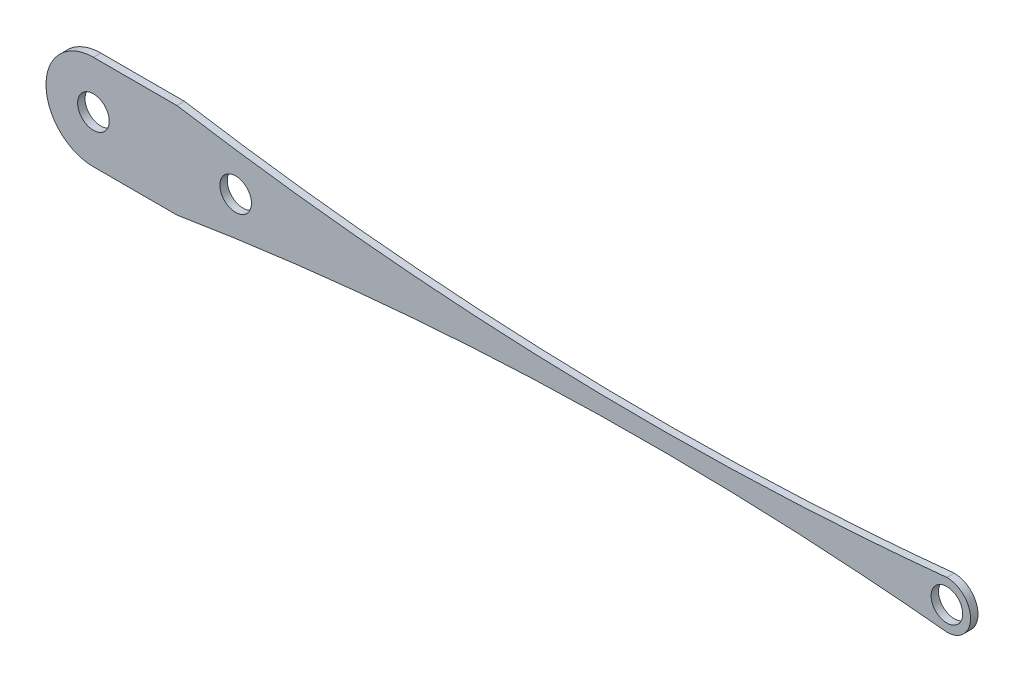
SolidWorks part; units mm, degrees
ref_plane "Front Plane" through (0, 0, 0) normal (0, 0, 1) x (1, 0, 0)
ref_plane "Top Plane" through (0, 0, 0) normal (0, 1, 0) x (1, 0, 0)
ref_plane "Right Plane" through (0, 0, 0) normal (1, 0, 0) x (0, 0, -1)
sketch "Sketch4" plane through (0, 0, 0) normal (0, 0, 1) x (1, 0, 0)
  line L0 (0, 0) -> (457.2, 0) construction
  line L1 (0, 25.4) -> (44.7423, 25.4)
  line L2 (0, -25.4) -> (44.7423, -25.4)
  arc A0 (0, 25.4) -> (0, -25.4) centre (0, 0) ccw
  circle A2 centre (0, 0) radius 8.4667
  circle A3 centre (76.2, 0) radius 8.4667
  circle A4 centre (457.2, 0) radius 8.4667
  arc A5 (457.2, -12.7) -> (457.2, 12.7) centre (457.2, 0) ccw
  arc A6 (44.7423, 25.4) -> (52.6769, 24.1289) centre (44.7423, 0) cw
  arc A7 (52.6769, -24.1289) -> (44.7423, -25.4) centre (44.7423, 0) cw
  spline S0 degree 2 poles (44.7423, 25.4) (249.9499, -8.0007) (457.2, 12.7) knots 0 0 0 1 1 1
  spline S1 degree 2 poles (44.7423, -25.4) (249.9499, 8.0007) (457.2, -12.7) knots 0 0 0 1 1 1
  point P3 (228.6, 0)
  dimension "D3" = 16.9333
  dimension "D5" = 25.4
  dimension "D1" = 50.8
  dimension "D2" = 457.2
  dimension "D6" = 19.05
  dimension "D7" = 19.05
  dimension "D8" = 76.2
extrude "Boss-Extrude2" add sketch "Sketch4" along normal blind 3.9688 contours L2 S1 A5 S0 L1 A0 A2 A3 A4 region at (157.5127, 0, 0)
scale "Scale1" scale about centroid uniform scaling yes scale factor 0.75
